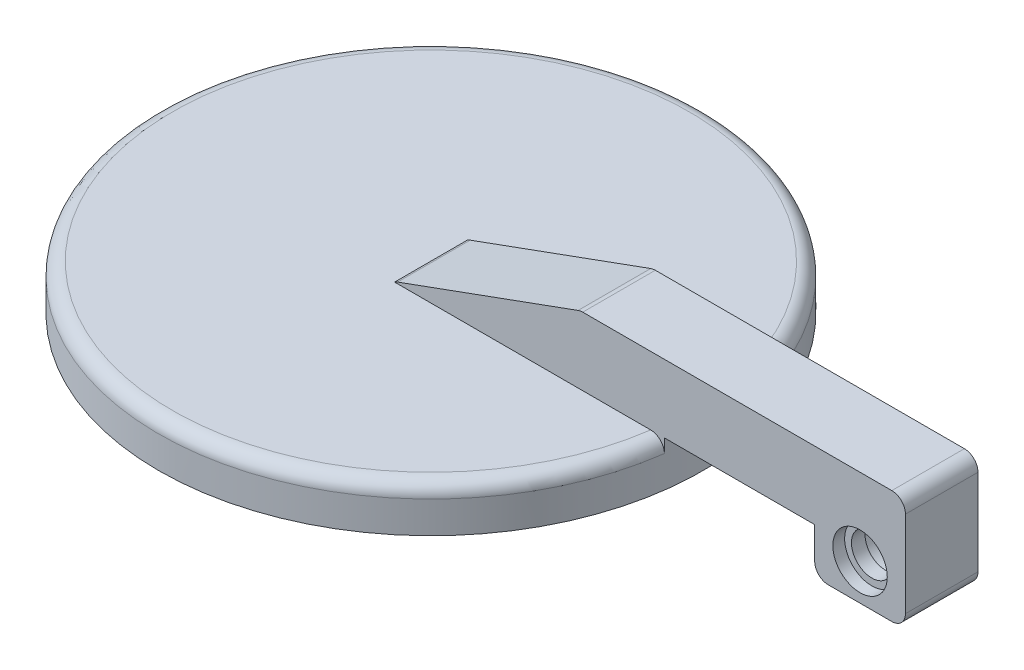
SolidWorks part; units mm, degrees
ref_plane "Front Plane" through (0, 0, 0) normal (0, 0, 1) x (1, 0, 0)
ref_plane "Top Plane" through (0, 0, 0) normal (0, 1, 0) x (1, 0, 0)
ref_plane "Right Plane" through (0, 0, 0) normal (1, 0, 0) x (0, 0, -1)
sketch "Sketch2" plane through (0, 0, 0) normal (0, 0, 1) x (1, 0, 0)
  line L7 (0, 0) -> (30, 0)
  line L8 (0, 0) -> (0, 5)
  line L9 (0, 5) -> (30, 5)
  line L10 (30, 0) -> (30, 5)
  dimension "D1" = 5
  dimension "D2" = 30
revolve "Revolve1" add sketch "Sketch2" angle 360 about L8
sketch "Sketch3" plane through (0, 5, 0) normal (0, 1, 0) x (1, 0, 0)
  line L0 (0, -10) -> (0, 10) construction
  line L1 (0, 10) -> (35, 10)
  line L2 (35, 10) -> (35, 6)
  line L3 (35, 6) -> (0, 6)
  line L4 (0, 10) -> (0, 6)
  line L5 (0, -10) -> (35, -10)
  line L6 (35, -10) -> (35, -6)
  line L7 (35, -6) -> (0, -6)
  line L8 (0, -6) -> (0, -10)
  line L9 (0, 4) -> (0, -4)
  line L10 (0, 4) -> (56.3, 4)
  line L11 (0, -4) -> (56.3, -4)
  line L12 (56.3, -4) -> (56.3, 4)
  point P4 (0, 0)
  point P13 (0, 0)
  circle M1 centre (0, 0) radius 30
  dimension "D1" = 20
  dimension "D2" = 35
  dimension "D3" = 4
  dimension "0.7" = 8
  dimension "D5" = 56.3
extrude "Boss-Extrude1" add sketch "Sketch3" along normal blind 7.5 contours L9 L11 L10 M1 | L11 L12 L10 M1 region at (14.9555, 5, 0) region at (43.1053, 5, 0)
sketch "Sketch4" plane through (0, 0, 0) normal (0, 0, 1) x (1, 0, 0)
  line L5 (35, 8.75) -> (37.8, 8.75) construction
  line L7 (56.3, 8.75) -> (37.8, 8.75) construction
  line L8 (56.3, 12.5) -> (56.3, 5) construction
  line L10 (-0.1339, 5) -> (20.4721, 12.5)
  line L11 (29.7321, 5) -> (-30, 5) construction
  line L12 (0, 12.5) -> (56.3, 12.5) construction
  line L13 (0, 5) -> (29.7321, 5) construction
  line L14 (20.4721, 12.5) -> (0, 12.5)
  line L15 (0, 12.5) -> (-0.1339, 5)
  circle A0 centre (37.8, 8.75) radius 2
  dimension "D3" = 4
  dimension "D1" = 20
  dimension "D2" = 18.5
extrude "Cut-Extrude1" cut sketch "Sketch4" against normal mid plane 30 contours L14 L15 L10
sketch "Sketch6" plane through (0, 5, 0) normal (0, -1, 0) x (1, 0, 0)
  line L6 (56.3, 4) -> (46.3, 4)
  line L7 (56.3, 4) -> (56.3, -4) construction
  line L8 (29.7321, 4) -> (56.3, 4) construction
  line L9 (46.3, 4) -> (46.3, -4)
  line L10 (29.7321, -4) -> (56.3, -4) construction
  line L11 (46.3, -4) -> (56.3, -4)
  line L12 (56.3, -4) -> (56.3, 4)
  dimension "D1" = 10
extrude "Boss-Extrude2" add sketch "Sketch6" along normal blind 5
sketch "Sketch7" plane through (0, 0, 4) normal (0, 0, 1) x (1, 0, 0)
  line L0 (51.3, 4) -> (51.3, 0) construction
  line L2 (56.3, 0) -> (46.3, 0) construction
  circle A0 centre (51.3, 4) radius 3
  dimension "D2" = 6
  dimension "D1" = 4
extrude "Cut-Extrude2" cut sketch "Sketch7" against normal blind 10
fillet "Fillet2" radius 1.5 6 edges at (46.3, 0, 0) (56.3, 0, 0) (56.3, 12.5, 0) (20.4721, 12.5, 0) (0, 5.0487, 0) (-30, 5, 0)
sketch "Sketch9" plane through (0, 0, -4) normal (0, 0, -1) x (-1, 0, 0)
  circle A0 centre (-51.3, 4) radius 3
  circle A1 centre (-51.3, 4) radius 4
  dimension "D1" = 6
  dimension "D2" = 8
sketch "Sketch10" plane through (0, 0, 4) normal (0, 0, 1) x (1, 0, 0)
  circle A0 centre (51.3, 4) radius 3
  circle A1 centre (51.3, 4) radius 2.25
  dimension "D1" = 6
  dimension "D2" = 4.5
extrude "Boss-Extrude4" add sketch "Sketch10" along normal blind 1.5 from offset 2.8 offset against normal yes
sketch "Sketch11" plane through (0, 0, 1.2) normal (0, 0, -1) x (-1, 0, 0)
  circle A0 centre (-51.3, 4) radius 2.6
  circle A1 centre (-51.3, 4) radius 3
  dimension "D1" = 5.2
extrude "Boss-Extrude5" add sketch "Sketch11" along normal blind 5.2
sketch "Sketch12" plane through (0, 0, 0) normal (0, -1, 0) x (1, 0, 0)
  line L0 (0, 30) -> (0, 25.5) construction
  circle A0 centre (0, 0) radius 30 construction
  circle A1 centre (0, 27.75) radius 1.1
  circle A2 centre (19.6222, 19.6222) radius 1.1
  circle A3 centre (27.75, 0) radius 1.1
  circle A4 centre (19.6222, -19.6222) radius 1.1
  circle A5 centre (0, -27.75) radius 1.1
  circle A6 centre (-19.6222, -19.6222) radius 1.1
  circle A7 centre (-27.75, 0) radius 1.1
  circle A8 centre (-19.6222, 19.6222) radius 1.1
  point P24 (0, 0)
  dimension "D2" = 2.2
  dimension "D1" = 4.5
  dimension "D3" = 8
extrude "Cut-Extrude3" cut sketch "Sketch12" against normal blind 0.3
